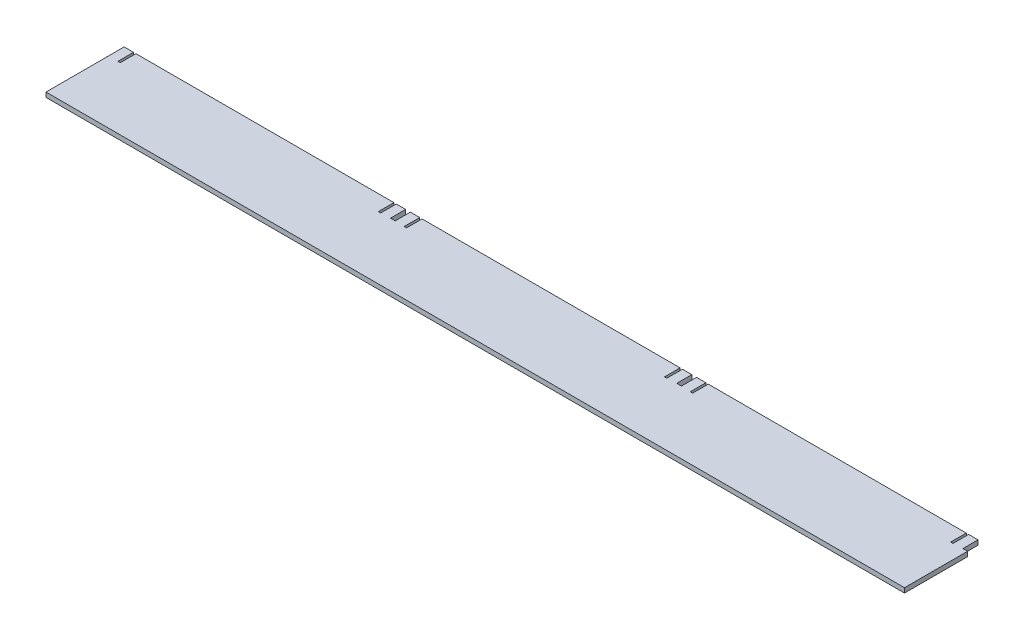
SolidWorks part; units mm, degrees
ref_plane "Front Plane" through (0, 0, 0) normal (0, 0, 1) x (1, 0, 0)
ref_plane "Top Plane" through (0, 0, 0) normal (0, 1, 0) x (1, 0, 0)
ref_plane "Right Plane" through (0, 0, 0) normal (1, 0, 0) x (0, 0, -1)
sketch "Sketch1" plane through (0, 0, 0) normal (0, 1, 0) x (1, 0, 0)
  line L0 (-84, 25) -> (-84, 15)
  line L1 (-90, -25) -> (90, -25)
  line L2 (-90, -25) -> (-90, 25)
  line L3 (-90, 25) -> (-84, 25)
  line L4 (90, -25) -> (90, 25)
  line L5 (-84, 15) -> (-82.5, 15)
  line L6 (-82.5, 15) -> (-82.5, 25)
  line L7 (82.5, 25) -> (82.5, 15)
  line L8 (82.5, 15) -> (84, 15)
  line L9 (84, 15) -> (84, 25)
  line L10 (-82.5, 25) -> (82.5, 25)
  line L11 (84, 25) -> (90, 25)
  point P4 (-90, 0)
  point P5 (0, 25)
  dimension "D1" = 50
  dimension "D2" = 180
  dimension "D3" = 6
  dimension "D4" = 1.5
  dimension "D5" = 10
extrude "Boss-Extrude1" add sketch "Sketch1" along normal mid plane 3
sketch "Sketch2" plane through (0, 0, 0) normal (0, 1, 0) x (1, 0, 0)
  line L0 (90, -25) -> (90, 25) construction
  line L1 (90, 15.3314) -> (93, 15.3314)
  line L2 (90, 15.3314) -> (90, -25)
  line L3 (90, -25) -> (93, -25)
  line L4 (93, 15.3314) -> (93, -25)
  line L5 (-90, -25) -> (90, -25) construction
  dimension "D1" = 3
extrude "Boss-Extrude2" add sketch "Sketch2" along normal mid plane 3
pattern_linear "LPattern2" count 3 spacing 183 along (1, 0, 0) of "Boss-Extrude1", "Boss-Extrude2"
sketch "Sketch3" [suppressed] plane through (0, 0, 0) normal (0, 1, 0) x (1, 0, 0)
  line L0 (-90, 25) -> (-90, -25) construction
  line L1 (-90, 15) -> (-93, 15)
  line L2 (-90, 15) -> (-90, -25)
  line L3 (-90, -25) -> (-93, -25)
  line L4 (-93, 15) -> (-93, -25)
  line L5 (-82.5, 15) -> (-84, 15) construction
  dimension "D1" = 3
extrude "Boss-Extrude3" [suppressed] add sketch "Sketch3" along normal mid plane 3
equation "\"mdfWidth\"= 3"
equation "\"cellSide\"= 180"
equation "\"mazeHeight\"= 50"
equation "\"slitHeight\"= 10"
equation "\"slitWidth\"= \"wallThickness\""
equation "\"gripWidth\"= 6"
equation "\"wallThickness\"= 1.5"
equation "\"D1@Sketch1\"= \"mazeHeight\""
equation "\"D2@Sketch1\"= \"cellSide\""
equation "\"D3@Sketch1\"= \"gripWidth\""
equation "\"D4@Sketch1\"= \"wallThickness\""
equation "\"D5@Sketch1\"= \"slitHeight\""
equation "\"D1@Boss-Extrude1\"= \"mdfWidth\""
equation "\"D1@Sketch2\"= \"mdfWidth\""
equation "\"D1@Boss-Extrude2\"= \"mdfWidth\""
equation "\"D1@LPattern1\"= 2"
equation "\"D3@LPattern1\"= \"cellSide\" + \"mdfWidth\""
equation "\"nbUnits\"=3"
equation "\"D1@LPattern2\"= \"nbUnits\""
equation "\"D1@Sketch3\"= \"mdfWidth\""
equation "\"D1@Boss-Extrude3\"= \"mdfWidth\""
equation "\"D3@LPattern2\"= \"cellSide\" + \"mdfWidth\""
